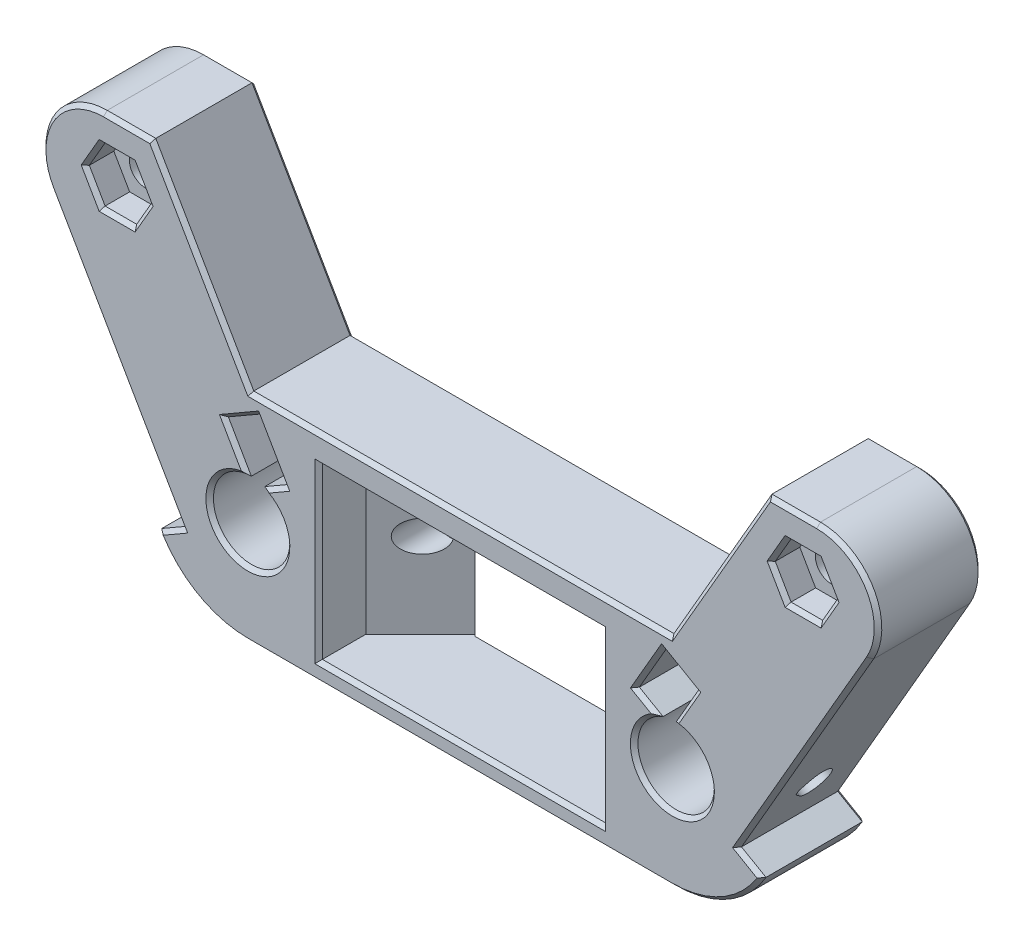
SolidWorks part; units mm, degrees
material "Custom Plastic"
ref_plane "Front Plane" through (0, 0, 0) normal (0, 0, 1) x (1, 0, 0)
ref_plane "Top Plane" through (0, 0, 0) normal (0, 1, 0) x (1, 0, 0)
ref_plane "Right Plane" through (0, 0, 0) normal (1, 0, 0) x (0, 0, -1)
sketch "Sketch1" plane through (0, 0, 0) normal (0, 0, 1) x (1, 0, 0)
  line L0 (0, 0) -> (-22.5, 0) construction
  line L1 (-22.5, -8) -> (22.5, -8) construction
  line L2 (0, -8) -> (0, 30) construction
  line L3 (-29.4282, -4) -> (-46.9282, 26.3109)
  line L4 (-46.9282, 26.3109) -> (-40.5385, 30)
  line L5 (-40.5385, 30) -> (-32.6614, 30)
  line L6 (0, 0) -> (22.5, 0) construction
  line L7 (46.9282, 26.3109) -> (40.5385, 30)
  line L8 (29.4282, -4) -> (46.9282, 26.3109)
  line L9 (-22.5, 0) -> (-36.3564, 24) construction
  line L10 (9, -9) -> (-9, -9)
  line L11 (9, -9) -> (9, 9)
  line L12 (9, 9) -> (-9, 9)
  line L13 (-9, -9) -> (-9, 9)
  line L14 (9, -9) -> (-9, 9) construction
  line L15 (9, 9) -> (-9, -9) construction
  line L16 (-36.3564, 24) -> (36.3564, 24) construction
  line L17 (36.3564, 24) -> (22.5, 0) construction
  line L18 (-29.4282, -4) -> (-32.0263, -5.5)
  line L19 (29.4282, -4) -> (32.0263, -5.5)
  line L20 (-22.5, -11) -> (22.5, -11)
  line L21 (-32.6614, 30) -> (-22.2691, 12)
  line L22 (-22.2691, 12) -> (22.2691, 12)
  line L23 (22.2691, 12) -> (32.6614, 30)
  line L24 (32.6614, 30) -> (40.5385, 30)
  circle A0 centre (-22.5, 0) radius 4.05
  arc A1 (-29.4282, -4) -> (-22.5, -8) centre (-22.5, 0) ccw construction
  arc A2 (29.4282, -4) -> (22.5, -8) centre (22.5, 0) cw construction
  circle A3 centre (22.5, 0) radius 4.05
  circle A4 centre (-36.3564, 24) radius 1.7
  circle A5 centre (36.3564, 24) radius 1.7
  arc A6 (-32.0263, -5.5) -> (-22.5, -11) centre (-22.5, 0) ccw
  arc A7 (22.5, -11) -> (32.0263, -5.5) centre (22.5, 0) ccw
  point P33 (0, 12)
  dimension "D1" = 8.1
  dimension "D2" = 8
  dimension "D10" = 3.4
  dimension "D11" = 3
  dimension "D3" = 45
  dimension "D4" = 120
  dimension "D5" = 18
  dimension "D6" = 18
  dimension "D7" = 24
  dimension "D8" = 35
  dimension "D9" = 30
  dimension "D12" = 23
  dimension "D13" = 14.2
extrude "Boss-Extrude1" add sketch "Sketch1" along normal blind 11
sketch "Sketch11" plane through (0, 0, 11) normal (0, 0, 1) x (1, 0, 0)
  line L1 (15, 9) -> (-15, 9)
  line L2 (15, 9) -> (15, -9)
  line L3 (15, -9) -> (-15, -9)
  line L4 (-15, 9) -> (-15, -9)
  line L5 (15, 9) -> (-15, -9) construction
  line L6 (15, -9) -> (-15, 9) construction
  point P0 (0, 0)
  dimension "D1" = 30
  dimension "D2" = 18
extrude "Cut-Extrude9" cut sketch "Sketch11" against normal blind 5
ref_axis "Axis1" through (-22.5, 0, 11) along (0, 0, -1)
sketch "Sketch6" plane through (-23.8032, -13.7428, 0) normal (-0.866, -0.5, 0) x (0, 0, 1)
  line L0 (0, 16.75) -> (11, 16.75) construction
  line L1 (0, 46.25) -> (0, 11.25) construction
  line L2 (11, 46.25) -> (11, 11.25) construction
  line L3 (11, 11.25) -> (0, 11.25) construction
  line L4 (5.5, 16.75) -> (6.6314, 15.6186) construction
  line L5 (6.6314, 15.6186) -> (7.42, 16.4073)
  line L6 (5.5, 16.75) -> (6.6314, 17.8814) construction
  line L7 (6.6314, 17.8814) -> (7.42, 17.0927)
  line L8 (7.42, 17.0927) -> (7.42, 16.4073)
  arc A0 (6.6314, 17.8814) -> (6.6314, 15.6186) centre (5.5, 16.75) ccw
  point P14 (7.42, 16.75)
  dimension "D1" = 3.2
  dimension "D2" = 5.5
  dimension "D3" = 1.92
extrude "Cut-Extrude4" cut sketch "Sketch6" against normal blind 16
sketch "Sketch7" plane through (-23.8032, -13.7428, 0) normal (-0.866, -0.5, 0) x (0, 0, 1)
  line L0 (11, 19.65) -> (11, 13.85)
  line L1 (3.6257, 19.65) -> (1.9514, 16.75)
  line L2 (1.9514, 16.75) -> (3.6257, 13.85)
  line L3 (3.6257, 13.85) -> (11, 13.85)
  line L4 (7.5993, 14.9325) -> (8.6486, 16.75) construction
  line L5 (8.6486, 16.75) -> (7.5993, 18.5675) construction
  line L6 (11, 19.65) -> (3.6257, 19.65)
  line L7 (11, 46.25) -> (11, 11.25) construction
  circle A0 centre (5.3, 16.75) radius 2.9 construction
  point P1 (5.5, 16.75)
  dimension "D1" = 5.8
  dimension "D2" = 0.2
extrude "Cut-Extrude5" cut sketch "Sketch7" against normal blind 4 from offset 10 offset against normal yes
sketch "Sketch8" plane through (-23.8032, -13.7428, 0) normal (-0.866, -0.5, 0) x (0, 0, 1)
  line L0 (5.5, 16.75) -> (7.6213, 14.6287) construction
  line L1 (7.6213, 14.6287) -> (9.1, 16.1074)
  line L2 (5.5, 16.75) -> (7.6213, 18.8713) construction
  line L3 (7.6213, 18.8713) -> (9.1, 17.3926)
  line L4 (9.1, 17.3926) -> (9.1, 16.1074)
  arc A0 (7.6213, 18.8713) -> (7.6213, 14.6287) centre (5.5, 16.75) ccw
  circle A1 centre (5.5, 16.75) radius 1.6 construction
  point P9 (9.1, 16.75)
  dimension "D1" = 6
  dimension "D2" = 3.6
extrude "Cut-Extrude6" [suppressed] cut sketch "Sketch8" against normal blind 3
mirror "Mirror2" about plane through (0, 0, 0) normal (1, 0, 0) of "Cut-Extrude6", "Cut-Extrude5", "Cut-Extrude4"
sketch "Sketch9" plane through (0, 0, 11) normal (0, 0, 1) x (1, 0, 0)
  line L1 (-43.4289, 20.25) -> (-46.9282, 26.3109)
  line L4 (0, 0) -> (0, 30) construction
  line L6 (-46.9282, 26.3109) -> (-40.5385, 30)
  line L7 (-40.5385, 30) -> (-37.7998, 30)
  line L8 (40.5385, 30) -> (37.7998, 30)
  line L11 (46.9282, 26.3109) -> (40.5385, 30)
  line L12 (43.4289, 20.25) -> (46.9282, 26.3109)
  arc A3 (-37.7998, 30) -> (-43.4289, 20.25) centre (-37.7998, 23.5) ccw
  arc A4 (37.7998, 30) -> (43.4289, 20.25) centre (37.7998, 23.5) cw
  dimension "D3" = 6.5
extrude "Cut-Extrude7" cut sketch "Sketch9" against normal through all
sketch "Sketch10" plane through (0, 0, 11) normal (0, 0, 1) x (1, 0, 0)
  line L1 (39.705, 24) -> (38.0307, 26.9)
  line L2 (38.0307, 26.9) -> (34.6821, 26.9)
  line L3 (34.6821, 26.9) -> (33.0078, 24)
  line L4 (33.0078, 24) -> (34.6821, 21.1)
  line L5 (34.6821, 21.1) -> (38.0307, 21.1)
  line L6 (38.0307, 21.1) -> (39.705, 24)
  line L7 (-33.0078, 24) -> (-34.6821, 26.9)
  line L8 (-34.6821, 26.9) -> (-38.0307, 26.9)
  line L9 (-38.0307, 26.9) -> (-39.705, 24)
  line L10 (-39.705, 24) -> (-38.0307, 21.1)
  line L11 (-38.0307, 21.1) -> (-34.6821, 21.1)
  line L12 (-34.6821, 21.1) -> (-33.0078, 24)
  circle A1 centre (36.3564, 24) radius 2.9 construction
  circle A4 centre (-36.3564, 24) radius 2.9 construction
  dimension "D1" = 5.8
extrude "Cut-Extrude8" cut sketch "Sketch10" against normal blind 3
chamfer "Chamfer1" distance 0.4 angle 45 40 edges at (23.7484, 6.1623, 11) (23.2359, 9.2746, 11) (20.0538, 7.7631, 11) (19.8573, 4.528, 11) (23.1912, -3.9906, 11) (-20.0538, 7.7631, 11) (-23.2359, 9.2746, 11) (-23.7484, 6.1623, 11) (-23.1912, -3.9906, 11) (-19.8573, 4.528, 11) (36.4286, 8.125, 11) (-36.4286, 8.125, 11) (-43.4289, 26.75, 11) (-35.2306, 30, 11) (43.4289, 26.75, 11) (30.7272, -4.75, 11) (28, -9.5263, 11) (0, -11, 11) (-28, -9.5263, 11) (-30.7272, -4.75, 11) (-27.4652, 21, 11) (0, 12, 11) (27.4652, 21, 11) (35.2306, 30, 11) (0, -9, 11) (15, 0, 11) (0, 9, 11) (-15, 0, 11) (38.8679, 25.45, 11) (36.3564, 26.9, 11) (33.8449, 25.45, 11) (33.8449, 22.55, 11) (36.3564, 21.1, 11) (38.8679, 22.55, 11) (-33.8449, 25.45, 11) (-36.3564, 26.9, 11) (-38.8679, 25.45, 11) (-38.8679, 22.55, 11) (-36.3564, 21.1, 11) (-33.8449, 22.55, 11)
chamfer "Chamfer2" distance 0.4 angle 45 22 edges at (38.0564, 24, 0) (9, 0, 0) (-9, 0, 0) (-18.45, 0, 0) (18.45, 0, 0) (-34.6564, 24, 0) (-43.4289, 26.75, 0) (-36.4286, 8.125, 0) (36.4286, 8.125, 0) (43.4289, 26.75, 0) (-35.2306, 30, 0) (-30.7272, -4.75, 0) (-28, -9.5263, 0) (0, -11, 0) (28, -9.5263, 0) (30.7272, -4.75, 0) (27.4652, 21, 0) (0, 12, 0) (-27.4652, 21, 0) (35.2306, 30, 0) (0, -9, 0) (0, 9, 0)
chamfer "Chamfer3" distance 6 angle 45 2 edges at (-9, 0, 6) (9, 0, 6)
sketch "Sketch12" plane through (0, 0, 0) normal (0, 0, -1) x (-1, 0, 0)
  line L0 (-12, 0) -> (12, 0) construction
  circle A0 centre (12, 0) radius 1.65
  circle A1 centre (-12, 0) radius 1.65
  dimension "D1" = 3.3
  dimension "D2" = 24
extrude "Cut-Extrude10" cut sketch "Sketch12" against normal through all
